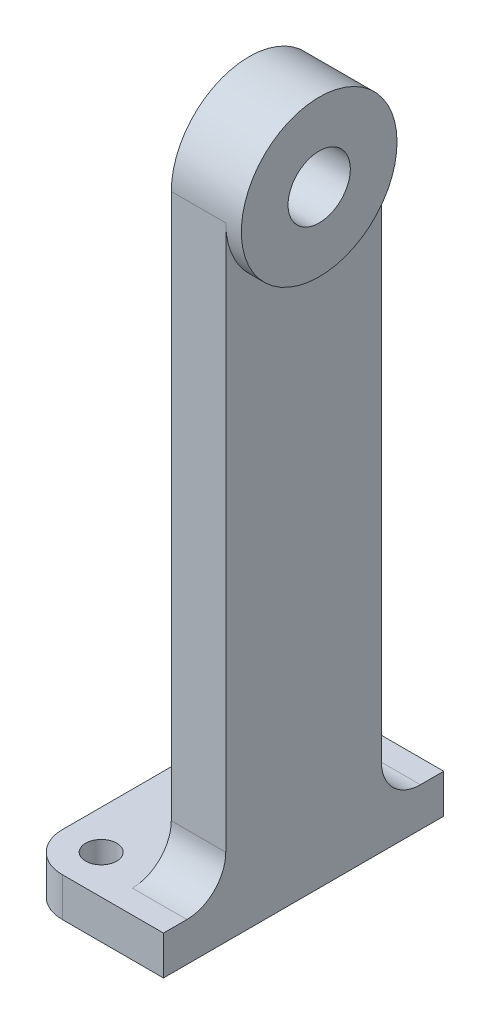
SolidWorks part; units mm, degrees
ref_plane "Front" through (0, 0, 0) normal (0, 0, 1) x (1, 0, 0)
ref_plane "Top" through (0, 0, 0) normal (0, 1, 0) x (1, 0, 0)
ref_plane "Right" through (0, 0, 0) normal (1, 0, 0) x (0, 0, -1)
sketch "Esquisse1" plane through (0, 0, 0) normal (0, 1, 0) x (1, 0, 0)
  line L1 (45, -90) -> (-20, -90)
  line L2 (45, -90) -> (45, 90)
  line L3 (45, 90) -> (-20, 90)
  line L4 (-45, -65) -> (-45, 65)
  line L5 (45, -90) -> (-45, 90) construction
  line L6 (45, 90) -> (-45, -90) construction
  arc A0 (-20, -90) -> (-45, -65) centre (-20, -65) cw
  arc A1 (-20, 90) -> (-45, 65) centre (-20, 65) ccw
  circle A2 centre (-20, 65) radius 10
  circle A3 centre (-20, -65) radius 10
  point P0 (0, 0)
  dimension "D3" = 25
  dimension "D4" = 20
  dimension "D1" = 180
  dimension "D2" = 90
extrude "Boss.-Extru.1" add sketch "Esquisse1" along normal blind 25
sketch "Esquisse2" plane through (45, 0, 0) normal (1, 0, 0) x (0, 0, -1)
  line L0 (0, 0) -> (0, 400) construction
  line L1 (-50, 400) -> (-50, 50)
  line L2 (-90, 25) -> (90, 25) construction
  line L3 (50, 400) -> (50, 50)
  line L4 (-75, 25) -> (75, 25)
  circle A0 centre (0, 400) radius 50
  circle A1 centre (0, 400) radius 20
  arc A2 (-50, 50) -> (-75, 25) centre (-75, 50) cw
  arc A3 (50, 50) -> (75, 25) centre (75, 50) ccw
  line M5 (90, 25) -> (-90, 25)
  dimension "D2" = 100
  dimension "D3" = 40
  dimension "D4" = 25
  dimension "D1" = 400
extrude "Boss.-Extru.2" add sketch "Esquisse2" against normal blind 35 contours L4 L0 A0 L1 A2 | L0 A3 L3 A0 M5 region at (45, 191.7627, 25.681) region at (45, 191.7627, -25.681)
extrude "Boss.-Extru.3" add sketch "Esquisse2<4>" along normal blind 10 and the other way up to surface (35 mm away) contours A0 A1 region at (45, 448.5858, 0) other way up to face at (10, 148.2741, 0)
sketch "Esquisse2<4>" plane through (45, 0, 0) normal (1, 0, 0) x (0, 0, -1) same geometry as "Esquisse2"
